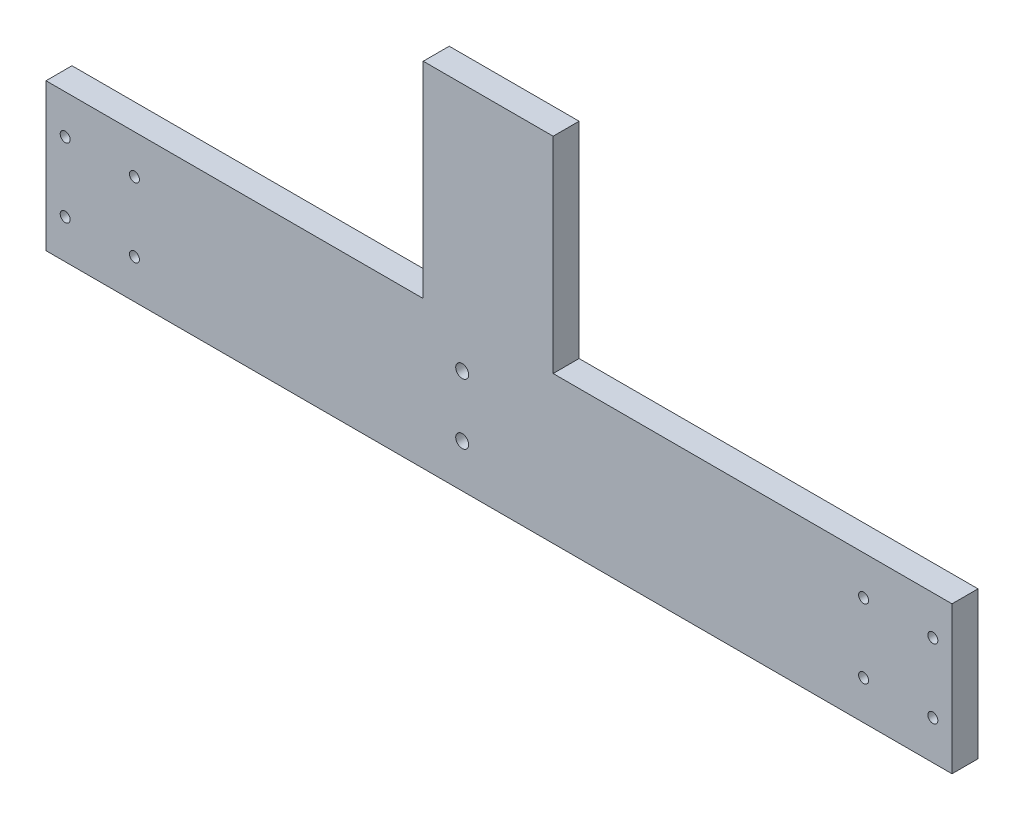
SolidWorks part; units mm, degrees
ref_plane "Plan de face" through (0, 0, 0) normal (0, 0, 1) x (1, 0, 0)
ref_plane "Plan de dessus" through (0, 0, 0) normal (0, 1, 0) x (1, 0, 0)
ref_plane "Plan de droite" through (0, 0, 0) normal (1, 0, 0) x (0, 0, -1)
sketch "Esquisse1" plane through (0, 0, 0) normal (0, 0, 1) x (1, 0, 0)
  line L0 (-104.63, 17) -> (-17.5, 17)
  line L1 (104.63, 17) -> (12.5, 17)
  line L2 (-104.63, 17) -> (-104.63, -17)
  line L3 (-104.63, -17) -> (104.63, -17)
  line L4 (104.63, 17) -> (104.63, -17)
  line L6 (-17.5, 17) -> (-17.5, 64.471)
  line L7 (-17.5, 64.471) -> (12.5, 64.471)
  line L8 (12.5, 17) -> (12.5, 64.471)
  dimension "D1" = 209.26
  dimension "D2" = 34
  dimension "D3" = 104.63
  dimension "D5" = 47.471
  dimension "D6" = 30
  dimension "D7" = 87.13
extrude "Boss.-Extru.1" add sketch "Esquisse1" along normal blind 6
sketch "Esquisse2" plane through (0, 0, 6) normal (0, 0, 1) x (1, 0, 0)
  line L0 (0, 49.0616) -> (0, -42.9956) construction
  line L1 (-104.63, 17) -> (-104.63, -17) construction
  line L3 (-104.63, -17) -> (104.63, -17) construction
  line L4 (-17.5, 17) -> (-104.63, 17) construction
  line L5 (-104.63, 17) -> (-104.63, -17) construction
  circle A0 centre (-100.2, 8) radius 1.15
  circle A1 centre (-84.2, 8) radius 1.15
  circle A2 centre (-84.2, -8) radius 1.15
  circle A3 centre (-100.2, -8) radius 1.15
  circle A4 centre (100.2, -8) radius 1.15
  circle A5 centre (84.2, -8) radius 1.15
  circle A6 centre (84.2, 8) radius 1.15
  circle A7 centre (100.2, 8) radius 1.15
  circle A8 centre (-8.5, 7) radius 1.5
  circle A9 centre (-8.5, -7) radius 1.5
  dimension "D1" = 2.3
  dimension "D2" = 2.3
  dimension "D3" = 2.3
  dimension "D4" = 2.3
  dimension "D12" = 3
  dimension "D14" = 3
  dimension "D5" = 4.43
  dimension "D6" = 9
  dimension "D7" = 9
  dimension "D8" = 16
  dimension "D9" = 16
  dimension "D10" = 16
  dimension "D11" = 16
  dimension "D13" = 10
  dimension "D15" = 10
  dimension "D16" = 14
  dimension "D17" = 8.5
  dimension "D18" = 4.43
extrude "Enlèv. mat.-Extru.1" cut sketch "Esquisse2" against normal blind 6
